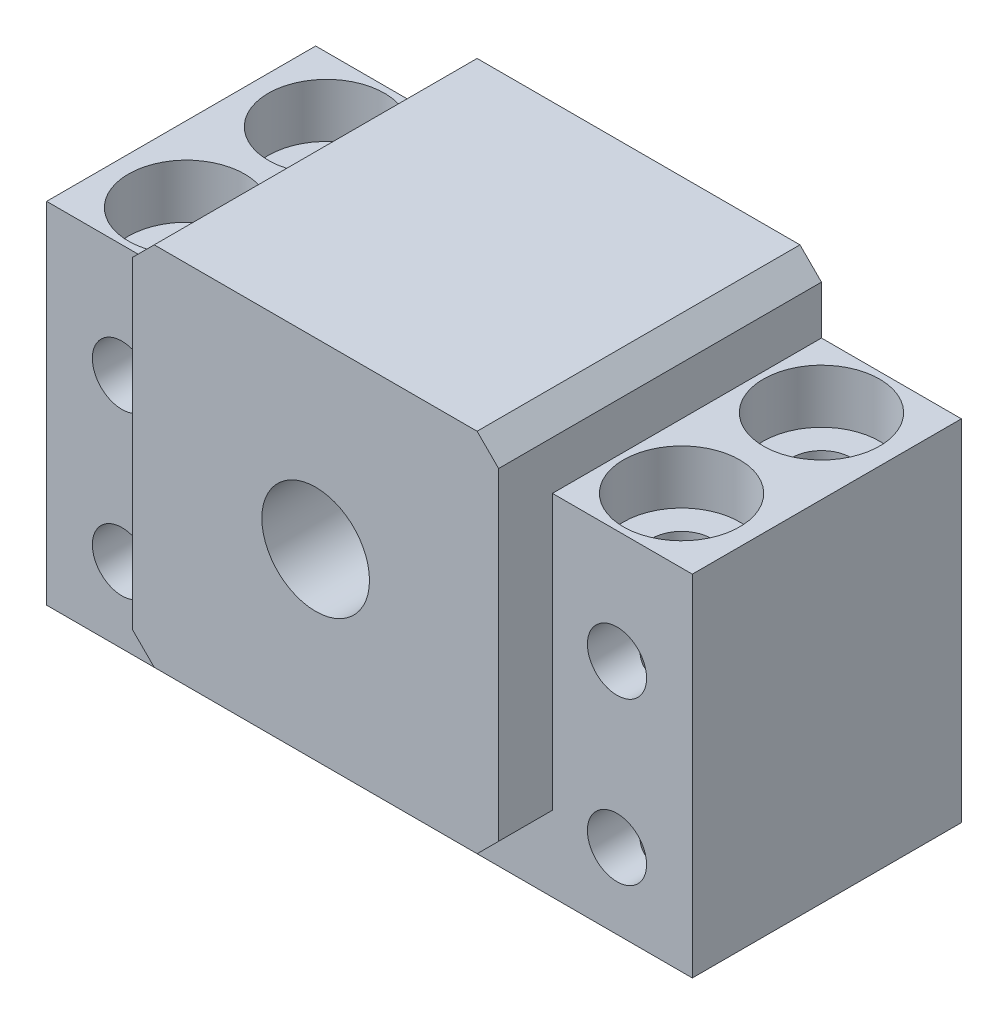
SolidWorks part; units mm, degrees
ref_plane "Front Plane" through (0, 0, 0) normal (0, 0, 1) x (1, 0, 0)
ref_plane "Top Plane" through (0, 0, 0) normal (0, 1, 0) x (1, 0, 0)
ref_plane "Right Plane" through (0, 0, 0) normal (1, 0, 0) x (0, 0, -1)
sketch "Sketch1" plane through (0, 0, 0) normal (0, 0, 1) x (1, 0, 0)
  line L0 (0, 0) -> (-17, 0) construction
  line L5 (0, 0) -> (0, 17) construction
  line L6 (15, 17) -> (-15, 17)
  line L7 (-15, 17) -> (-17, 15)
  line L8 (-17, 15) -> (-17, -15)
  line L9 (0, 0) -> (-17, 17) construction
  line L10 (-15, 17) -> (-17, 17) construction
  line L11 (-17, 15) -> (-17, 17) construction
  line L12 (17, 15) -> (17, 17) construction
  line L13 (15, 17) -> (17, 17) construction
  line L14 (0, 0) -> (17, 17) construction
  line L15 (17, 15) -> (17, -15)
  line L16 (15, 17) -> (17, 15)
  line L17 (15, -17) -> (17, -15)
  line L18 (-15, -17) -> (-17, -15)
  line L19 (15, -17) -> (-15, -17)
  circle A0 centre (0, 0) radius 5
  point P3 (-16, 16)
  point P9 (0, 0)
  point P10 (0, 0)
  point P11 (0, 0)
  point P19 (17, 0)
  dimension "D1" = 10
  dimension "D2" = 34
  dimension "D3" = 2
extrude "Boss-Extrude1" add sketch "Sketch1" along normal blind 5
sketch "Sketch2" plane through (0, 0, 0) normal (0, 0, -1) x (-1, 0, 0)
  line L0 (15, 17) -> (-15, 17)
  line L1 (-15, 17) -> (-17, 15)
  line L2 (-17, 15) -> (-17, 10.5)
  line L3 (-17, -15) -> (-17, 15) construction
  line L4 (-17, 10.5) -> (-30, 10.5)
  line L5 (-30, 10.5) -> (-30, -22)
  line L6 (-30, -22) -> (30, -22)
  line L7 (0, 17) -> (0, -22) construction
  line L8 (-23, 0) -> (-23, -15) construction
  line L9 (23, -15) -> (-23, -15) construction
  line L10 (0, 0) -> (-23, 0) construction
  line L11 (30, 10.5) -> (30, -22)
  line L12 (17, 10.5) -> (30, 10.5)
  line L13 (17, 15) -> (17, 10.5)
  line L14 (15, 17) -> (17, 15)
  circle A0 centre (0, 0) radius 5 construction
  circle A1 centre (0, 0) radius 5
  circle A2 centre (-23, 0) radius 2.75
  circle A3 centre (-23, -15) radius 2.75
  circle A4 centre (23, -15) radius 2.75
  circle A5 centre (23, 0) radius 2.75
  point P24 (0, -15)
  point P29 (0, 0)
  dimension "D3" = 5.5
  dimension "D1" = 32.5
  dimension "D2" = 39
  dimension "D4" = 60
  dimension "D5" = 46
  dimension "D6" = 15
extrude "Boss-Extrude2" add sketch "Sketch2" along normal blind 25
sketch "Sketch3" plane through (0, -22, 0) normal (0, -1, 0) x (1, 0, 0)
  line L0 (0, 0) -> (0, -25) construction
  line L1 (23, -19) -> (-23, -19) construction
  line L2 (23, -19) -> (23, -6) construction
  line L3 (23, -6) -> (-23, -6) construction
  line L4 (-23, -19) -> (-23, -6) construction
  line L5 (23, -19) -> (-23, -6) construction
  line L6 (23, -6) -> (-23, -19) construction
  line L7 (30, -25) -> (-30, -25) construction
  line L8 (-25.75, -6) -> (-25.75, 0) construction
  line L9 (-20.25, -6) -> (-20.25, 0) construction
  circle A0 centre (-23, -6) radius 2.75
  circle A1 centre (-23, -19) radius 2.75
  circle A2 centre (23, -6) radius 2.75
  circle A3 centre (23, -19) radius 2.75
  point P0 (0, -12.5)
  point P19 (-20.25, -1.2074)
  point P20 (0, 0)
  point P23 (0, 0)
  point P24 (0, 0)
  dimension "D1" = 13
  dimension "D2" = 6
extrude "Cut-Extrude1" cut sketch "Sketch3" against normal through all
sketch "Sketch4" plane through (0, 10.5, 0) normal (0, 1, 0) x (1, 0, 0)
  circle A0 centre (23, 6) radius 5.4
  circle A1 centre (23, 19) radius 5.4
  circle A2 centre (-23, 19) radius 5.4
  circle A3 centre (-23, 6) radius 5.4
  point P8 (0, 0)
  dimension "D1" = 10.8
extrude "Cut-Extrude2" cut sketch "Sketch4" against normal blind 5
